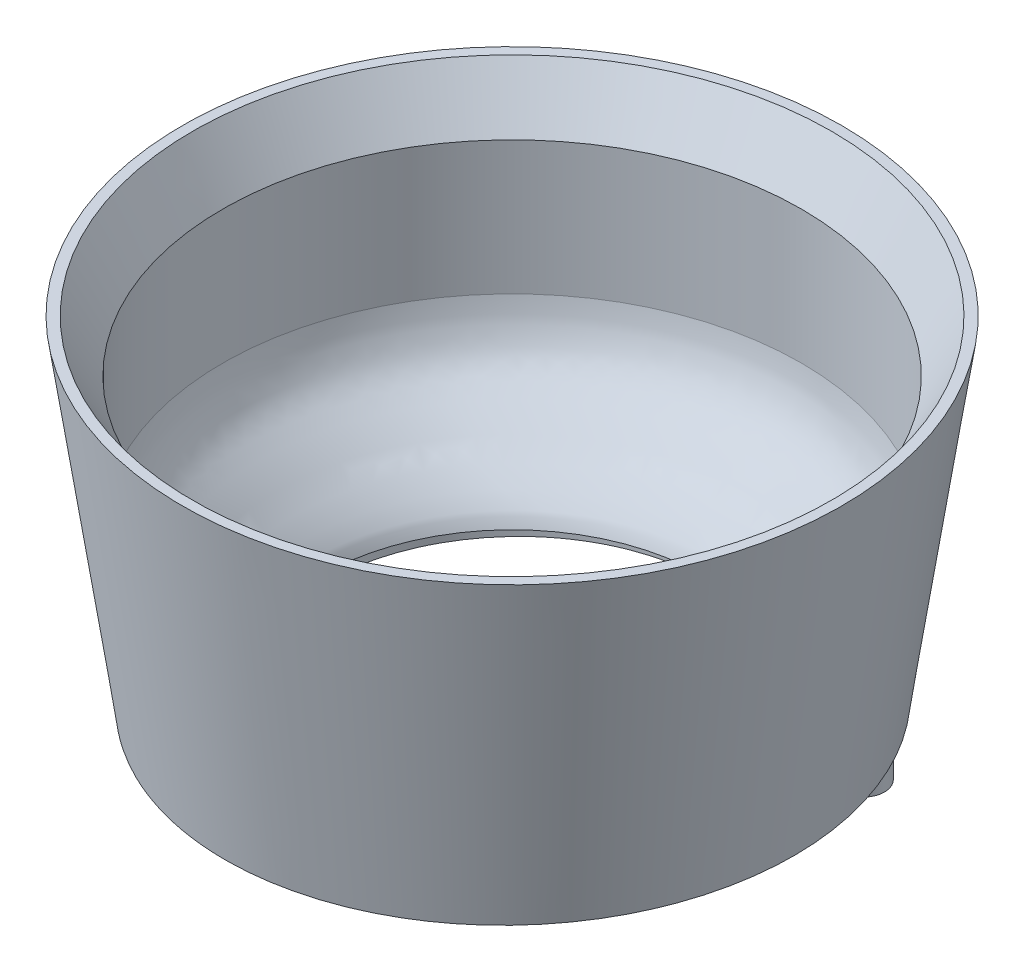
SolidWorks part; units mm, degrees
material "ABS PC"
ref_plane "Front Plane" through (0, 0, 0) normal (0, 0, 1) x (1, 0, 0)
ref_plane "Top Plane" through (0, 0, 0) normal (0, 1, 0) x (1, 0, 0)
ref_plane "Right Plane" through (0, 0, 0) normal (1, 0, 0) x (0, 0, -1)
sketch "Sketch1" plane through (0, 0, 0) normal (1, 0, 0) x (0, 0, -1)
  line L0 (26.0878, 274.978) -> (26.0878, 232.1195)
  line L2 (40.135, 299.274) -> (-40.135, 299.274) construction
  line L5 (0, 324) -> (3.2968, 324)
  line L8 (0, 324) -> (0, 0) construction
  line L9 (26.0878, 262.3641) -> (26.0878, 259.4973) construction
  line L12 (40.135, 302.9291) -> (40.135, 295.6188)
  line L16 (0, 0) -> (51.9362, 327.9125) construction
  line L17 (0, 324) -> (0, 332) construction
  line L18 (26.0878, 274.978) -> (26.0878, 268.978) construction
  line L19 (26.0878, 268.978) -> (26.0878, 248.978) construction
  line L20 (26.0878, 268.978) -> (42.6019, 268.978) construction
  line L21 (26.0878, 274.978) -> (43.5522, 274.978) construction
  line L22 (26.0878, 248.978) -> (39.4342, 248.978) construction
  line L23 (0, 0) -> (-51.9362, 327.9125) construction
  line L24 (-47.4003, 299.274) -> (-47.4003, 268.978) construction
  line L25 (-47.4003, 268.978) -> (-42.6019, 268.978) construction
  line L26 (0, 332) -> (0, 76.96) construction
  line L27 (0, 76.96) -> (400, 76.96) construction
  line L28 (0, 76.96) -> (-400, 76.96) construction
  line L29 (-200, 76.96) -> (-200, 183.96) construction
  line L30 (200, 76.96) -> (200, 183.96) construction
  line L31 (-200, 183.96) -> (-200, 182.57) construction
  line L32 (-200, 182.57) -> (400, 182.57) construction
  line L33 (-200, 182.57) -> (-400, 182.57) construction
  line L38 (0, 186.1152) -> (0, 324)
  line L39 (26.0878, 232.1195) -> (26.0878, 182.57) construction
  line L41 (21.6442, 226.0993) -> (26.0878, 226.0993)
  line L42 (26.0878, 226.0993) -> (26.0878, 186.1152)
  line L43 (26.0878, 186.1152) -> (0, 186.1152)
  line L44 (0, 0) -> (575.122, 0) construction
  arc A0 (-298.7691, 144.7791) -> (305.6579, 129.6043) centre (0, 0) cw construction
  spline S0 degree 3 poles (21.6442, 226.0993) (21.9584, 226.1509) (22.4049, 226.153) (22.896, 226.3321) (23.44, 226.7494) (24.2443, 227.2014) (25.0066, 227.9724) (25.5796, 228.9522) (25.8622, 230.393) (26.0228, 231.4436) (26.0878, 232.1195) knots 0 0 0 0 0.091924 0.112491 0.205673 0.333714 0.459267 0.602423 0.748839 1 1 1 1
  spline S1 degree 3 poles (3.2968, 324) (4.1972, 323.8396) (5.699, 323.816) (7.6935, 323.4297) (9.2722, 323.1563) (10.7507, 322.8538) (12.1816, 322.5577) (13.6372, 322.313) (14.8643, 321.9117) (15.9115, 321.5662) (16.81, 321.2491) (17.7339, 321.0149) (18.8379, 320.6416) (19.931, 320.1935) (21.0686, 319.6948) (22.141, 319.2627) (23.2156, 318.6856) (24.4371, 318.1163) (25.6762, 317.3518) (27.1066, 316.7518) (28.4318, 315.7832) (29.7322, 314.8939) (31.058, 313.93) (32.1959, 312.8581) (33.3378, 311.8503) (34.4539, 310.9646) (35.3895, 309.8867) (36.5078, 309.0949) (37.2942, 308.0208) (38.1233, 307.1238) (38.9048, 306.0961) (39.4724, 304.6349) (40.2774, 303.734) (40.135, 302.9291) knots 0 0 0 0 0.061585 0.100795 0.136831 0.1697 0.202569 0.235438 0.269088 0.289473 0.309858 0.333319 0.353706 0.388423 0.412965 0.437514 0.46634 0.495168 0.528354 0.564387 0.59925 0.638593 0.670824 0.709635 0.743897 0.773612 0.805519 0.839783 0.864953 0.89467 0.922395 0.951224 1 1 1 1
  spline S2 degree 3 poles (40.135, 295.6188) (39.9636, 294.7131) (39.7869, 293.3689) (39.1095, 291.6901) (38.6019, 290.4599) (37.8418, 289.2392) (36.9195, 288.2279) (35.9232, 287.2651) (34.974, 286.2515) (33.8311, 285.3463) (32.8233, 284.2966) (31.8701, 283.2868) (30.7668, 282.4387) (29.8742, 281.4644) (28.8604, 280.5152) (28.0567, 279.5119) (27.1438, 278.5569) (26.4968, 277.0287) (26.0081, 275.8567) (26.0878, 274.978) knots 0 0 0 0 0.108356 0.15601 0.210945 0.263562 0.322855 0.370186 0.4254 0.484692 0.539909 0.595126 0.646549 0.701764 0.749093 0.808384 0.85195 0.901837 1 1 1 1
  point P10 (0, 299.274)
  point P63 (0, 299.274)
  dimension "D3" = 9
  dimension "D1" = 40.135
  dimension "D2" = 324
  dimension "D4" = 8
  dimension "D5" = 3.2968
  dimension "D6" = 4.4435
  dimension "D7" = 6.0202
  dimension "D8" = 7.7403
  dimension "D9" = 6
  dimension "D10" = 20
  dimension "D11" = 9.317
  dimension "D12" = 10.7504
  dimension "D13" = 255.04
  dimension "D14" = 107
  dimension "D15" = 107
  dimension "D16" = 332
  dimension "D17" = 105.61
  dimension "D18" = 105.61
  dimension "D19" = 12.1838
  dimension "D20" = 13.6172
  dimension "D21" = 15.0506
  dimension "D22" = 15.9106
  dimension "D23" = 16.7707
  dimension "D24" = 17.7739
  dimension "D25" = 18.6341
  dimension "D26" = 20.0676
  dimension "D27" = 21.0708
  dimension "D28" = 22.0743
  dimension "D29" = 23.2209
  dimension "D30" = 24.3677
  dimension "D31" = 25.6578
  dimension "D32" = 27.0911
  dimension "D33" = 28.3811
  dimension "D34" = 29.8146
  dimension "D35" = 30.9613
  dimension "D36" = 32.2513
  dimension "D37" = 33.3981
  dimension "D38" = 34.4014
  dimension "D39" = 35.4048
  dimension "D40" = 36.5516
  dimension "D41" = 37.2681
  dimension "D42" = 38.1282
  dimension "D43" = 38.8449
  dimension "D44" = 39.4183
  dimension "D45" = 39.9917
  dimension "D46" = 323.8567
  dimension "D47" = 323.7133
  dimension "D48" = 323.4267
  dimension "D49" = 323.1399
  dimension "D50" = 322.8533
  dimension "D51" = 322.5666
  dimension "D52" = 322.2799
  dimension "D53" = 321.8499
  dimension "D54" = 321.5632
  dimension "D55" = 321.2765
  dimension "D56" = 320.9899
  dimension "D57" = 320.7031
  dimension "D58" = 320.1297
  dimension "D59" = 319.6998
  dimension "D60" = 319.2698
  dimension "D61" = 318.6965
  dimension "D62" = 318.1231
  dimension "D63" = 317.4064
  dimension "D64" = 316.6897
  dimension "D65" = 315.8296
  dimension "D66" = 314.8263
  dimension "D67" = 313.9663
  dimension "D68" = 312.8195
  dimension "D69" = 311.8162
  dimension "D70" = 310.9562
  dimension "D71" = 309.9528
  dimension "D72" = 308.9493
  dimension "D73" = 308.0893
  dimension "D74" = 307.086
  dimension "D75" = 306.0826
  dimension "D76" = 304.9359
  dimension "D77" = 303.9325
  dimension "D78" = 302.9291
sketch "Sketch2" plane through (0, 0, 0) normal (1, 0, 0) x (0, 0, -1)
  line L0 (0, 324) -> (3.2968, 324) construction
  line L1 (26.5078, 274.997) -> (26.5078, 273.8486)
  line L2 (40.5477, 295.5407) -> (40.5477, 314.2386)
  line L3 (40.135, 295.6188) -> (40.135, 302.9302) construction
  line L4 (40.135, 295.6188) -> (26.0878, 274.978) construction
  line L5 (0, 324.42) -> (3.4084, 324.42) construction
  line L6 (3.2968, 324) -> (40.135, 302.9302) construction
  line L7 (3.4084, 324.42) -> (40.555, 303.1738) construction
  line L8 (26.0878, 274.978) -> (26.0878, 232.1195) construction
  line L9 (40.555, 295.4895) -> (26.435, 274.7417) construction
  line L10 (0, 5) -> (0, 407.9498) construction
  line L12 (26.5078, 273.8486) -> (38.5078, 273.8486) construction
  line L13 (26.5078, 274.997) -> (26.5078, 232.1195) construction
  line L14 (38.5078, 273.8486) -> (45.76, 323.5611) construction
  line L17 (40.5477, 314.2386) -> (45.93, 323.5611) construction
  line L18 (45.93, 323.5611) -> (45.76, 323.5611) construction
  line L19 (0, 186.1152) -> (0, 324) construction
  line L20 (0, 324) -> (0, 332) construction
  line L21 (40.555, 295.4895) -> (40.555, 303.1738) construction
  line L22 (0, 5) -> (47.1644, 328.2999) construction
  line L23 (45.93, 323.5611) -> (46.473, 323.5611) construction
  line L24 (46.473, 323.5611) -> (39.2208, 273.8486) construction
  line L25 (39.2208, 273.8486) -> (26.5078, 273.8486)
  line L26 (44.7753, 321.5611) -> (46.1813, 321.5611)
  line L27 (44.7753, 321.5611) -> (40.5477, 314.2386)
  line L28 (46.1813, 321.5611) -> (39.2208, 273.8486)
  spline S0 degree 1 poles (40.5477, 295.5407) (26.5078, 274.997) knots 0 0 1 1 construction
  spline S1 degree 3 poles (40.135, 295.6188) (39.9636, 294.7131) (39.7869, 293.3689) (39.1095, 291.6901) (38.6019, 290.4599) (37.8418, 289.2392) (36.9195, 288.2279) (35.9232, 287.2651) (34.974, 286.2515) (33.8311, 285.3463) (32.8233, 284.2966) (31.8701, 283.2868) (30.7668, 282.4387) (29.8742, 281.4644) (28.8604, 280.5152) (28.0567, 279.5119) (27.1438, 278.5569) (26.4968, 277.0287) (26.0081, 275.8567) (26.0878, 274.978) knots 0 0 0 0 0.108356 0.15601 0.210945 0.263562 0.322855 0.370186 0.4254 0.484692 0.539909 0.595126 0.646549 0.701764 0.749093 0.808384 0.85195 0.901837 1 1 1 1 construction
  spline S2 degree 3 poles (40.5477, 295.5407) (40.4477, 295.0127) (40.2928, 293.9708) (39.9309, 292.5875) (39.5162, 291.5815) (39.1084, 290.578) (38.4397, 289.317) (37.3314, 288.0326) (36.3684, 287.1154) (35.6302, 286.3401) (35.0165, 285.7627) (34.3943, 285.2472) (33.6355, 284.5566) (32.9204, 283.7714) (32.1297, 282.9861) (31.4852, 282.4595) (30.915, 281.9635) (30.3717, 281.3913) (29.7828, 280.8046) (29.2276, 280.2622) (28.7248, 279.6749) (28.1804, 279.0397) (27.6518, 278.4702) (27.3081, 277.8768) (26.9952, 277.1272) (26.598, 276.1645) (26.4648, 275.4705) (26.5078, 274.997) knots 0 0 0 0 0.062544 0.125088 0.15636 0.187632 0.250176 0.31272 0.375264 0.406536 0.437808 0.46908 0.500352 0.562896 0.594168 0.62544 0.656713 0.687985 0.719257 0.750529 0.781801 0.813073 0.844345 0.875617 0.906889 0.938161 1.000705 1.000705 1.000705 1.000705
  point P38 (0, 328)
  dimension "D4" = 1.1484
  dimension "D5" = 8.3
  dimension "D6" = 30
  dimension "D7" = 45.93
  dimension "D8" = 40.39
  dimension "D9" = 8.3
  dimension "D10" = 40.5477
  dimension "D3" = 12
  dimension "D11" = 18.6979
  dimension "D12" = 2
  dimension "D13" = 5
  dimension "D1" = 0.42
  dimension "D2" = 0.42
revolve "Revolve6" add sketch "Sketch2" angle 360 about L10
sketch "Sketch3" plane through (0, 0, 0) normal (1, 0, 0) x (0, 0, -1)
  line L0 (44.1979, 321.5611) -> (40.5477, 314.2386) construction
  line L3 (46.1813, 321.5611) -> (-46.1813, 321.5611) construction
  line L4 (44.7753, 321.5611) -> (-44.7753, 321.5611) construction
  line L5 (40.5477, 314.2386) -> (-40.5477, 314.2386) construction
  line L6 (40.5477, 314.2386) -> (54.812, 333.8718)
  line L8 (54.812, 333.8718) -> (54.812, 347.837)
  line L9 (54.812, 347.837) -> (0, 347.837)
  line L10 (0, 347.837) -> (0, 311.6751)
  line L11 (0, 186.1152) -> (0, 324) construction
  line L12 (0, 311.6751) -> (40.5477, 311.6751)
  line L13 (40.5477, 311.6751) -> (40.5477, 314.2386)
  dimension "D1" = 36
  dimension "D2" = 54.812
revolve "Cut-Revolve1" [suppressed] cut sketch "Sketch3" angle 360 about L10
sketch "Sketch4" plane through (0, 273.8486, 0) normal (0, -1, 0) x (1, 0, 0)
  line L0 (0, 0) -> (31.1769, -18) construction
  line L1 (0, 0) -> (-36, 0) construction
  circle A0 centre (0, 0) radius 36 construction
  circle A1 centre (-36, 0) radius 3
  circle A2 centre (31.1769, -18) radius 3
  dimension "D1" = 72
  dimension "D3" = 6
  dimension "D4" = 6
  dimension "D2" = 210
extrude "Boss-Extrude1" add sketch "Sketch4" along normal blind 2
sketch "Sketch5" [suppressed] plane through (0, 263.8486, 0) normal (0, -1, 0) x (1, 0, 0)
  circle A0 centre (36, 0) radius 3.175
  circle A1 centre (-31.1769, 18) radius 3.175
  dimension "D1" = 6.35
  dimension "D2" = 6.35
extrude "Boss-Extrude2" [suppressed] add sketch "Sketch5" along normal blind 5
chamfer "Chamfer2" [suppressed] distance 9 angle 4
sketch "Sketch7" plane through (0, 0, 0) normal (1, 0, 0) x (0, 0, -1)
  line L0 (0, 5) -> (0, 407.9498) construction
  line L1 (26.5078, 273.8486) -> (39.2208, 273.8486) construction
  line L2 (39.2208, 273.8486) -> (39.2208, 272.3194)
  line L4 (26.5078, 273.8486) -> (26.5078, 274.3486)
  line L5 (26.5078, 274.3486) -> (39.2208, 274.3486)
  line L6 (39.2208, 274.3486) -> (39.2208, 273.8486)
  circle A0 centre (0, -0.122) radius 275.25 construction
  arc A1 (39.2208, 272.3194) -> (26.5078, 273.8486) centre (0, -0.122) ccw
  dimension "D1" = 550.5
  dimension "D2" = 0.5
revolve "Revolve7" add sketch "Sketch7" angle 360 about L10
sketch "Sketch13" plane through (0, 0, 0) normal (0, 0, 1) x (1, 0, 0)
  line L0 (0, 272.3194) -> (39.2208, 272.3194) construction
  line L2 (39.2208, 272.3194) -> (39.2208, 275.8194) construction
  line L5 (0, 274.8194) -> (7.0342, -1.0662) construction
  line L6 (39.2208, 275.8194) -> (39.2208, 265.8194) construction
  line L7 (39.2208, 265.8194) -> (19.2208, 265.8194)
  line L8 (19.2208, 265.8194) -> (19.2208, 277.4173)
  line L9 (39.2208, 265.8194) -> (42.2208, 265.8194)
  line L10 (42.2208, 265.8194) -> (42.2208, 275.4541)
  line L12 (-39.2208, 272.3194) -> (-39.2208, 273.8194) construction
  line L13 (39.2208, 275.8194) -> (-39.2208, 273.8194) construction
  line L15 (-39.2208, 272.3194) -> (39.2208, 272.3194) construction
  line L16 (39.2208, 272.3194) -> (-39.2208, 272.3194) construction
  arc A2 (42.2208, 275.4541) -> (19.2208, 277.4173) centre (7.0342, -1.0662) ccw
  point P17 (0, 272.3194)
  point P23 (0, 274.8194)
  dimension "D2" = 278.75
  dimension "D1" = 3.5
  dimension "D3" = 20
  dimension "D4" = 10
  dimension "D5" = 3
  dimension "D6" = 1.5
revolve "Cut-Revolve6" cut sketch "Sketch13" angle 360 about L5
extrude "Boss-Extrude3" add sketch "Sketch4<3>" against normal up to next and the other way blind 2
sketch "Sketch4<3>" plane through (0, 273.8486, 0) normal (0, -1, 0) x (1, 0, 0) same geometry as "Sketch4"
sketch "Sketch15" plane through (0, 271.8486, 0) normal (0, -1, 0) x (1, 0, 0)
  circle A0 centre (-36, 0) radius 1.5
  circle A1 centre (31.1769, -18) radius 1.5
  dimension "D1" = 3
  dimension "D2" = 3
extrude "Cut-Extrude3" cut sketch "Sketch15" against normal blind 6
sketch "Sketch16" plane through (0, 271.8486, 0) normal (0, -1, 0) x (1, 0, 0)
  circle A0 centre (-36, 0) radius 2
  circle A1 centre (31.1769, -18) radius 2
  dimension "D1" = 4
  dimension "D2" = 4
extrude "Cut-Extrude4" cut sketch "Sketch16" against normal blind 0.5
chamfer "Chamfer3" distance 0.55 angle 45 2 edges at (-36, 271.8486, -2) (31.1769, 271.8486, -20)
sketch "Sketch17" plane through (0, 321.5611, 0) normal (0, 1, 0) x (1, 0, 0)
  circle A0 centre (0, 0) radius 26.8
  dimension "D1" = 53.6
extrude "Cut-Extrude5" cut sketch "Sketch17" against normal through all
